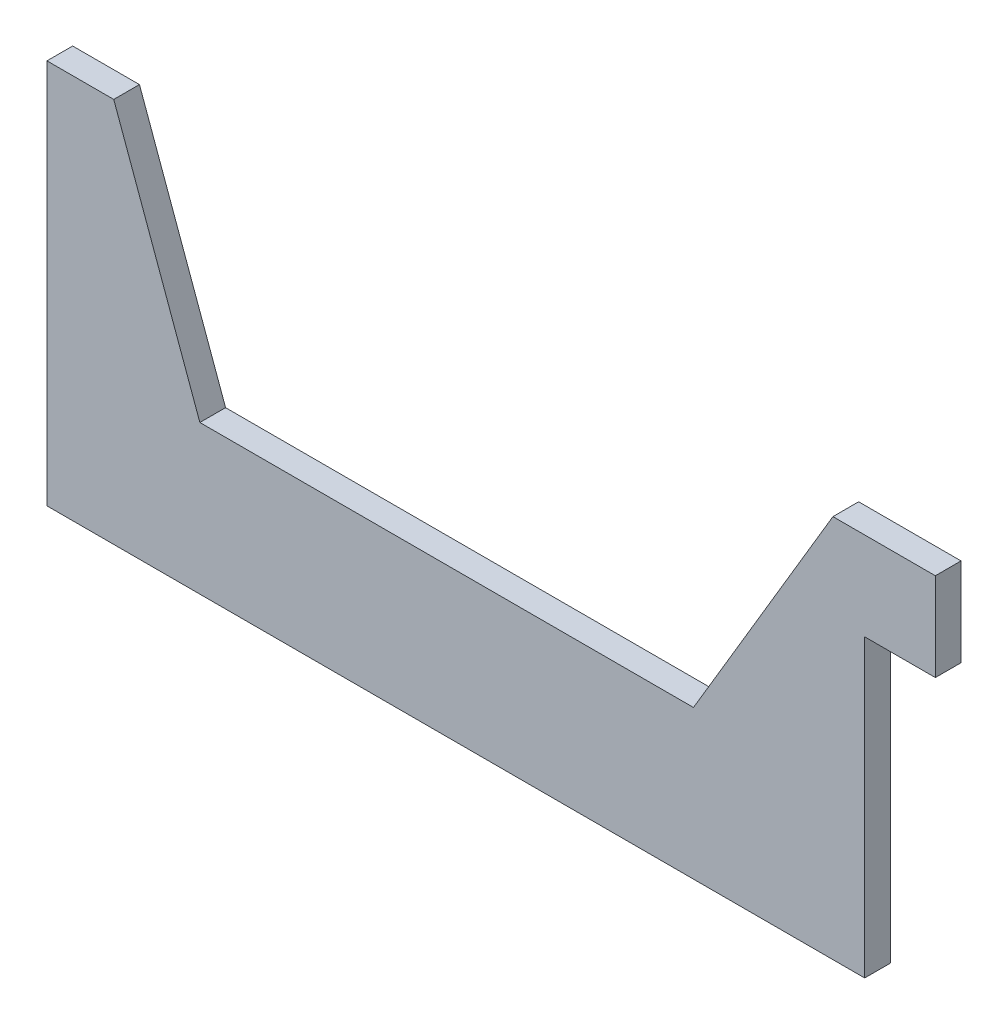
SolidWorks part; units mm, degrees
ref_plane "Front Plane" through (0, 0, 0) normal (0, 0, 1) x (1, 0, 0)
ref_plane "Top Plane" through (0, 0, 0) normal (0, 1, 0) x (1, 0, 0)
ref_plane "Right Plane" through (0, 0, 0) normal (1, 0, 0) x (0, 0, -1)
sketch "Sketch1" plane through (0, 0, 0) normal (0, 0, 1) x (1, 0, 0)
  line L2 (-60.75, -30) -> (-60.75, 30)
  line L11 (66.5497, 16) -> (77.5497, 16)
  line L18 (66.5497, -30) -> (66.5497, 16)
  line L21 (77.5497, 29.7321) -> (77.5497, 16)
  line L23 (-60.75, 30) -> (-50.3529, 30)
  line L24 (-50.3529, 30) -> (-36.9454, -6.8552)
  line L25 (-36.9454, -6.8552) -> (39.8971, -6.8552)
  line L26 (39.8971, -6.8552) -> (61.6068, 29.7321)
  line L27 (61.6068, 29.7321) -> (77.5497, 29.7321)
  line L29 (-60.75, -30) -> (66.5497, -30)
  point P13 (-60.75, 0)
  dimension "D1" = 138.3
  dimension "D2" = 11
  dimension "D3" = 46
  dimension "D4" = 60
extrude "Boss-Extrude1" add sketch "Sketch1" along normal mid plane 4
equation "\"wall_thick_ness\"=4"
equation "\"D1@Boss-Extrude1\"=\"wall_thick_ness\""
equation "\"back_boost\"=7"
equation "\"D1@Sketch1\"=\"back_boost\"+131.30mm"
